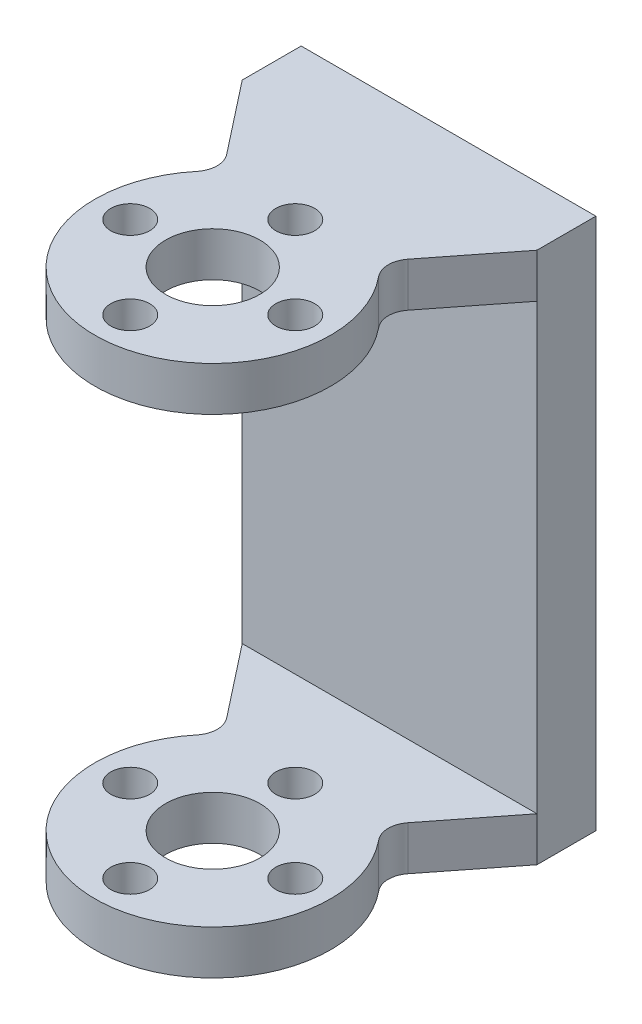
SolidWorks part; units mm, degrees
ref_plane "Front Plane" through (0, 0, 0) normal (0, 0, 1) x (1, 0, 0)
ref_plane "Top Plane" through (0, 0, 0) normal (0, 1, 0) x (1, 0, 0)
ref_plane "Right Plane" through (0, 0, 0) normal (1, 0, 0) x (0, 0, -1)
sketch "Sketch1" plane through (0, 0, 0) normal (0, 1, 0) x (1, 0, 0)
  line L2 (-12.5, 15) -> (-12.5, 20)
  line L3 (-12.5, 20) -> (12.5, 20)
  line L4 (12.5, 15) -> (12.5, 20)
  line L5 (-12.5, 15) -> (-6.6144, 7.5)
  line L6 (6.6144, 7.5) -> (12.5, 15)
  circle A3 centre (0, 0) radius 4
  arc A4 (-6.6144, 7.5) -> (6.6144, 7.5) centre (0, 0) ccw
  point P12 (-12.5, 0)
  point P13 (0, 20)
  dimension "D3" = 0
  dimension "D4" = 20
  dimension "D6" = 8
  dimension "D2" = 10
  dimension "D1" = 25
  dimension "D5" = 5
  dimension "D7" = 12.5
extrude "Boss-Extrude1" add sketch "Sketch1" along normal blind 45.15
sketch "Sketch2" plane through (-12.5, 0, 0) normal (-1, 0, 0) x (0, 0, 1)
  line L1 (25, 3.75) -> (-15, 3.75)
  line L2 (25, 3.75) -> (25, 41.4)
  line L3 (25, 41.4) -> (-15, 41.4)
  line L4 (-15, 3.75) -> (-15, 41.4)
  line L5 (-20, 45.15) -> (-20, 0) construction
  point P6 (-20, 22.575)
  point P7 (25, 22.575)
  dimension "D1" = 37.65
  dimension "D2" = 5
  dimension "D3" = 45
extrude "Cut-Extrude1" cut sketch "Sketch2" against normal through all
ref_plane "B mid plane" through (0, 22.575, 0) normal (0, -1, 0) x (-1, 0, 0)
sketch "Sketch3" plane through (0, 45.15, 0) normal (0, 1, 0) x (1, 0, 0)
  circle A0 centre (0, 7) radius 1.65
  circle A1 centre (0, 0) radius 4 construction
  dimension "D1" = 3.3
  dimension "D2" = 7
  dimension "D3" = 0
extrude "Cut-Extrude2" cut sketch "Sketch3" against normal through all
ref_axis "Axis1" through (0, 45.15, 0) along (0, -1, 0)
pattern_circular "CirPattern1" count 4 over 360 about axis through (0, 45.15, 0) along (0, -1, 0) of "Cut-Extrude2"
fillet "Fillet1" radius 2 4 edges at (6.6144, 43.275, -7.5) (6.6144, 1.875, -7.5) (-6.6144, 43.275, -7.5) (-6.6144, 1.875, -7.5)
